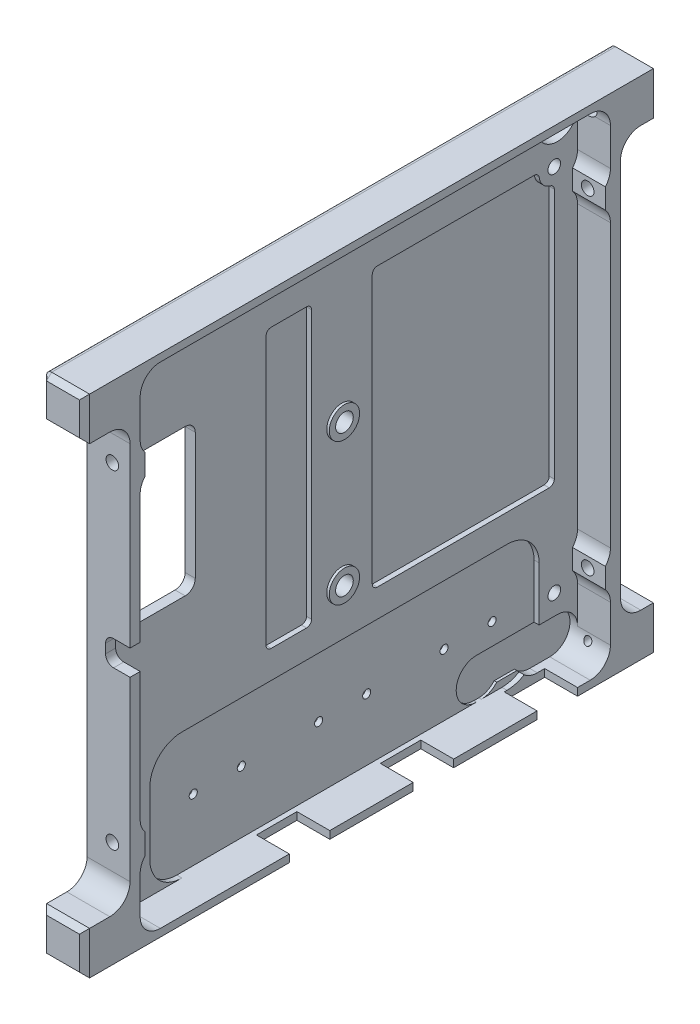
SolidWorks part; units mm, degrees
material "6061-T6 (SS)"
ref_plane "Front" through (0, 0, 0) normal (0, 0, 1) x (1, 0, 0)
ref_plane "Top" through (0, 0, 0) normal (0, 1, 0) x (1, 0, 0)
ref_plane "Right" through (0, 0, 0) normal (1, 0, 0) x (0, 0, -1)
sketch "Sketch1" plane through (0, 0, 0) normal (1, 0, 0) x (0, 0, -1)
  line L1 (0, 0) -> (-113.5, 0)
  line L2 (0, 0) -> (0, 100)
  line L3 (0, 100) -> (-113.5, 100)
  line L4 (-113.5, 0) -> (-113.5, 100)
  line L5 (-113.5, 91.5) -> (-104.5, 91.5)
  line L6 (-113.5, 91.5) -> (-113.5, 8.5)
  line L7 (-113.5, 8.5) -> (-104.5, 8.5)
  line L8 (-104.5, 91.5) -> (-104.5, 8.5)
  line L9 (0, 91.5) -> (-7.5, 91.5)
  line L10 (0, 91.5) -> (0, 8.5)
  line L11 (0, 8.5) -> (-7.5, 8.5)
  line L12 (-7.5, 91.5) -> (-7.5, 8.5)
  line L13 (-96.5, 91.5) -> (-15.5, 91.5)
  line L14 (-96.5, 91.5) -> (-96.5, 8.5)
  line L15 (-96.5, 8.5) -> (-15.5, 8.5)
  line L16 (-15.5, 91.5) -> (-15.5, 8.5)
  dimension "D1" = 113.5
  dimension "D2" = 100
  dimension "D3" = 8.5
  dimension "D4" = 8.5
  dimension "D5" = 8
  dimension "D6" = 8
  dimension "D7" = 9
  dimension "D8" = 7.5
extrude "Body" add sketch "Sketch1" along normal blind 8.5 contours L12 L9 L2 L3 L4 L5 L8 L7 L1 L11 L13 L16 L15 L14
fillet "RailFillet" radius 1 2 edges at (0, 0, 56.75) (0, 100, 56.75)
chamfer "FootChamfer" distance 1 angle 45 20 edges at (4.75, 0, 0) (8.5, 4.25, 0) (4.25, 8.5, 0) (0, 4.75, 0) (4.25, 91.5, 0) (8.5, 95.75, 0) (4.75, 100, 0) (0, 95.25, 0) (4.75, 100, 113.5) (8.5, 95.75, 113.5) (4.25, 91.5, 113.5) (0, 95.25, 113.5) (4.25, 8.5, 113.5) (8.5, 4.25, 113.5) (4.75, 0, 113.5) (0, 4.75, 113.5) (0.2929, 0.2929, 0) (0.2929, 99.7071, 0) (0.2929, 99.7071, 113.5) (0.2929, 0.2929, 113.5)
sketch "Sketch5" plane through (8.5, 0, 0) normal (1, 0, 0) x (0, 0, -1)
  line L1 (-96.5, 91.5) -> (-15.5, 91.5)
  line L2 (-96.5, 91.5) -> (-96.5, 8.5)
  line L3 (-96.5, 8.5) -> (-15.5, 8.5)
  line L4 (-15.5, 91.5) -> (-15.5, 8.5)
extrude "Boss-Extrude3" add sketch "Sketch5" against normal up to surface (8.5 mm away) up to face at (0, 50, 56.5)
sketch "Sketch6" plane through (8.5, 0, 0) normal (1, 0, 0) x (0, 0, -1)
  line L0 (-1, 100) -> (-112.5, 100) construction
  line L1 (-102.5, 98.5) -> (-9.5, 98.5)
  line L2 (-102.5, 98.5) -> (-102.5, 1.5)
  line L3 (-102.5, 1.5) -> (-9.5, 1.5)
  line L4 (-9.5, 98.5) -> (-9.5, 1.5)
  line L5 (-1, 0) -> (-112.5, 0) construction
  line L7 (-7.5, 91.5) -> (-7.5, 8.5) construction
  line L10 (-104.5, 91.5) -> (-104.5, 8.5) construction
  dimension "D1" = 1.5
  dimension "D2" = 1.5
  dimension "D3" = 2
  dimension "D4" = 2
extrude "Cut-Extrude3" cut sketch "Sketch6" against normal offset from surface (6.5 mm away) 2 up to face at (0, 50, 56.5)
sketch "Sketch4" plane through (8.5, 0, 0) normal (1, 0, 0) x (0, 0, -1)
  line L1 (-92.5, 90) -> (-19.5, 90)
  line L2 (-92.5, 90) -> (-92.5, 10)
  line L3 (-92.5, 10) -> (-19.5, 10)
  line L4 (-19.5, 90) -> (-19.5, 10)
  line L6 (-7.5, 91.5) -> (-7.5, 8.5) construction
  line L8 (-1, 100) -> (-112.5, 100) construction
  line L9 (-1, 0) -> (-112.5, 0) construction
  line L10 (-104.5, 91.5) -> (-104.5, 8.5) construction
  dimension "D1" = 12
  dimension "D2" = 10
  dimension "D3" = 10
  dimension "D4" = 12
ref_plane "Plane1" through (0, 50, 0) normal (0, 1, 0) x (1, 0, 0)
ref_plane "Plane2" through (0, 0, 56) normal (0, 0, -1) x (-1, 0, 0)
sketch "Sketch21" plane through (0, 0, 0) normal (1, 0, 0) x (0, 0, -1)
  line L0 (-98.1, 86.5) -> (-98.1, 13.5) construction
  line L1 (-98.1, 13.5) -> (-14.1, 13.5) construction
  line L2 (-14.1, 13.5) -> (-14.1, 86.5) construction
  line L3 (-14.1, 86.5) -> (-98.1, 86.5) construction
  line L4 (-14.1, 50) -> (-7.5, 50) construction
  line L6 (-7.5, 91.5) -> (-7.5, 8.5) construction
  line L7 (0, 99) -> (0, 92.5) construction
  line L8 (-14.1, 50) -> (-98.1, 50) construction
  line L9 (-56.1, 50) -> (-56.1, 36) construction
  line L10 (-7.5, 50) -> (-7.5, 0) construction
  line L11 (-112.5, 0) -> (-1, 0) construction
  line L12 (-1, 100) -> (-112.5, 100) construction
  line L13 (-7.5, 100) -> (-7.5, 50) construction
  line L16 (-56.1, 64) -> (-56.1, 50) construction
  point P3 (-14.1, 13.5)
  point P5 (-98.1, 86.5)
  point P7 (-98.1, 13.5)
  point P11 (-56.1, 36)
  point P25 (-14.1, 86.5)
  point P26 (-56.1, 64)
  dimension "D3" = 28
  dimension "D1" = 73
  dimension "D2" = 84
  dimension "D4" = 14.1
sketch "Sketch29" plane through (0, 0, 0) normal (0, 0, -1) x (-1, 0, 0)
  line L0 (-1, 92.5) -> (-7.5, 99)
  line L1 (-7.5, 99) -> (-1, 99)
  line L2 (-1, 99) -> (-4.25, 95.75)
hole_wizard "#8-36 Tapped Hole1" positions "Sketch30" profile "Sketch31" tap size "#8-36" standard "ANSI Inch"
sketch "Sketch30" plane through (0, 0, 0) normal (0, 0, -1) x (-1, 0, 0)
  point P0 (-4.25, 95.75)
sketch "Sketch31" plane through (4.25, 95.75, 0) normal (1, 0, 0) x (0, 1, 0)
  line L0 (0, 0) -> (0, 14.5878)
  line L1 (0, 14.5878) -> (1.7272, 13.55)
  line L2 (1.7272, 13.55) -> (1.7272, 0)
  line L5 (1.7272, 0) -> (0, 0)
  line L10 (0, 14.5878) -> (-1.7272, 13.55) construction
  line L11 (0, -6.35) -> (0, 107.95) construction
  dimension "Tap Drill Dia." = 3.4544
  dimension "Tap Drill Depth" = 13.55
  dimension "Drill Angle" = 118
cosmetic thread "Hole Thread1" parameters "D1"=10.5229, "D2"=4.1656
sketch "Sketch32" plane through (0, 0, 0) normal (0, 0, -1) x (-1, 0, 0)
  line L1 (-4.25, 1) -> (-4.25, 4.25) construction
  line L2 (-7.5, 1) -> (-1, 1) construction
  line L3 (-4.25, 4.25) -> (-7.5, 4.25) construction
  line L4 (-7.5, 7.5) -> (-7.5, 1) construction
  point P1 (-4.25, 4.25)
hole_wizard "#8-36 Tapped Hole2" [suppressed] positions "Sketch33" profile "Sketch34" tap size "#8-36" standard "ANSI Inch"
sketch "Sketch33" plane through (0, 0, 0) normal (0, 0, -1) x (-1, 0, 0)
  point P0 (-4.25, 4.25)
sketch "Sketch34" plane through (4.25, 4.25, 0) normal (1, 0, 0) x (0, 1, 0)
  line L0 (0, 0) -> (0, 11.4878)
  line L1 (0, 11.4878) -> (1.7272, 10.45)
  line L2 (1.7272, 10.45) -> (1.7272, 0)
  line L5 (1.7272, 0) -> (0, 0)
  line L10 (0, 11.4878) -> (-1.7272, 10.45) construction
  line L11 (0, -6.35) -> (0, 107.95) construction
  dimension "Tap Drill Dia." = 3.4544
  dimension "Tap Drill Depth" = 10.45
  dimension "Drill Angle" = 118
cosmetic thread "Hole Thread2" [suppressed] parameters "D1"=8.33, "D2"=4.1656
sketch "Sketch44" [suppressed] plane through (2.5, 0, 0) normal (1, 0, 0) x (0, 0, -1)
  point P0 (-17.45, 3.7)
  point P2 (-17.45, 7.7)
sketch "Sketch57" plane through (2, 0, 0) normal (1, 0, 0) x (0, 0, -1)
  line L0 (-9.5, 1.5) -> (-9.5, 98.5) construction
  line L1 (-9.5, 84.5) -> (-10.5, 84.5)
  line L2 (-9.5, 84.5) -> (-9.5, 80.5)
  line L3 (-9.5, 80.5) -> (-10.5, 80.5)
  line L4 (-10.5, 84.5) -> (-10.5, 80.5)
  line L5 (-102.5, 1.5) -> (-102.5, 98.5) construction
  line L6 (-9.5, 19.5) -> (-10.5, 19.5)
  line L7 (-9.5, 19.5) -> (-9.5, 15.5)
  line L8 (-9.5, 15.5) -> (-10.5, 15.5)
  line L9 (-10.5, 19.5) -> (-10.5, 15.5)
  line L10 (-10.5, 19.5) -> (-101.5, 19.5)
  line L11 (-10.5, 19.5) -> (-10.5, 15.5)
  line L12 (-10.5, 15.5) -> (-101.5, 15.5)
  line L13 (-101.5, 19.5) -> (-101.5, 15.5)
  line L14 (-10.5, 84.5) -> (-101.5, 84.5)
  line L15 (-10.5, 84.5) -> (-10.5, 80.5)
  line L16 (-10.5, 80.5) -> (-101.5, 80.5)
  line L17 (-101.5, 84.5) -> (-101.5, 80.5)
  line L18 (-101.5, 84.5) -> (-102.5, 84.5)
  line L19 (-101.5, 84.5) -> (-101.5, 80.5)
  line L20 (-101.5, 80.5) -> (-102.5, 80.5)
  line L21 (-102.5, 84.5) -> (-102.5, 80.5)
  line L22 (-9.5, 50) -> (-102.5, 50) construction
  line L23 (-101.5, 19.5) -> (-102.5, 19.5)
  line L24 (-101.5, 19.5) -> (-101.5, 15.5)
  line L25 (-101.5, 15.5) -> (-102.5, 15.5)
  line L26 (-102.5, 19.5) -> (-102.5, 15.5)
  line L28 (-102.5, 82.5) -> (-102.5, 50) construction
  line L29 (-102.5, 50) -> (-102.5, 17.5) construction
  line L31 (-9.5, 98.5) -> (-9.5, 1.5) construction
  dimension "D1" = 4
  dimension "D2" = 4
  dimension "D3" = 1
  dimension "D4" = 32.5
  dimension "D5" = 32.5
extrude "Boss-Extrude24" add sketch "Sketch57" along normal up to surface (6.5 mm away) contours L18 L21 L20 L17 | L23 L26 L25 L13 | L6 L9 L8 L7 | L1 L4 L3 L2 up to face at (8.5, 50, 56)
fillet "Fillet5" radius 4 8 edges at (5.25, 84.5, 102.5) (5.25, 19.5, 102.5) (5.25, 80.5, 102.5) (5.25, 15.5, 102.5) (5.25, 19.5, 9.5) (5.25, 15.5, 9.5) (5.25, 80.5, 9.5) (5.25, 84.5, 9.5)
sketch "Sketch59" plane through (0, 0, 7.5) normal (0, 0, -1) x (-1, 0, 0)
  line L0 (-5, 91.5) -> (-5, 82.5) construction
  line L2 (-5, 82.5) -> (-5, 17.5) construction
  line L3 (-5, 17.5) -> (-5, 8.5) construction
  line L5 (0, 91.5) -> (0, 8.5) construction
  line L6 (-8.5, 91.5) -> (0, 91.5) construction
  line L7 (-8.5, 8.5) -> (0, 8.5) construction
  dimension "D1" = 65
  dimension "D2" = 5
hole_wizard "M3x0.5 Tapped Hole1" positions "Sketch60" profile "Sketch61" tap size "M3x0.5" standard "ANSI Metric" end condition through all
sketch "Sketch60" plane through (0, 0, 7.5) normal (0, 0, -1) x (-1, 0, 0)
  point P0 (-5, 82.5)
  point P3 (-5, 17.5)
sketch "Sketch61" plane through (5, 82.5, 7.5) normal (1, 0, 0) x (0, 1, 0)
  line L0 (0, 0) -> (0, 106)
  line L1 (0, 106) -> (1.25, 106)
  line L2 (1.25, 106) -> (1.25, 0)
  line L5 (1.25, 0) -> (0, 0)
  line L11 (0, -6.35) -> (0, 107.95) construction
  dimension "Thru Tap Drill Dia." = 2.5
  dimension "Thru Tap Drill Depth" = 106
cosmetic thread "Hole Thread5" parameters "D2"=3
cosmetic thread "Hole Thread6" parameters "D2"=3
sketch "Sketch62" [suppressed] plane through (1, 0, 0) normal (1, 0, 0) x (0, 0, -1)
  line L1 (-11.25, 13.5) -> (-11.25, 1.5)
  line L2 (-11.5, 1.5) -> (-100, 1.5) construction
  line L3 (-11.25, 1.5) -> (-15.75, 1.5)
  line L4 (-15.75, 1.5) -> (-15.75, 10.1459)
  circle A0 centre (-14.75, 86.5) radius 3.5
  circle A1 centre (-14.75, 13.5) radius 3.5
  circle A2 centre (-97.75, 13.5) radius 3.5
  circle A3 centre (-97.75, 86.5) radius 3.5
  circle A4 centre (-97.75, 86.5) radius 1.25 construction
  circle A5 centre (-97.75, 13.5) radius 1.25 construction
  circle A6 centre (-14.75, 13.5) radius 1.25 construction
  circle A7 centre (-14.75, 86.5) radius 1.25 construction
  circle A8 centre (-97.75, 86.5) radius 1.25
  circle A9 centre (-97.75, 13.5) radius 1.25
  circle A10 centre (-14.75, 13.5) radius 1.25
  circle A11 centre (-14.75, 86.5) radius 1.25
  dimension "D1" = 7
  dimension "D2" = 4.5
fillet "Fillet7" radius 4 4 edges at (5.25, 98.5, 102.5) (5.25, 1.5, 102.5) (5.25, 1.5, 9.5) (5.25, 98.5, 9.5)
hole_wizard "M3x0.5 Tapped Hole2" positions "Sketch67" profile "Sketch68" tap size "M3x0.5" standard "ANSI Metric"
sketch "Sketch67" plane through (0, 0, 0) normal (-1, 0, 0) x (0, 0, 1)
  point P0 (14.1, 13.5)
  point P3 (14.1, 86.5)
  point P12 (98.1, 86.5)
  point P15 (98.1, 13.5)
sketch "Sketch68" plane through (0, 13.5, 14.1) normal (0, 1, 0) x (0, 0, 1)
  line L0 (0, 0) -> (0, 8.2511)
  line L1 (0, 8.2511) -> (1.25, 7.5)
  line L2 (1.25, 7.5) -> (1.25, 0)
  line L5 (1.25, 0) -> (0, 0)
  line L10 (0, 8.2511) -> (-1.25, 7.5) construction
  line L11 (0, -6.35) -> (0, 107.95) construction
  dimension "Tap Drill Dia." = 2.5
  dimension "Tap Drill Depth" = 7.5
  dimension "Drill Angle" = 118
cosmetic thread "Hole Thread17" parameters "D1"=2.5, "D2"=3
cosmetic thread "Hole Thread18" parameters "D1"=2.5, "D2"=3
cosmetic thread "Hole Thread21" parameters "D1"=2.5, "D2"=3
cosmetic thread "Hole Thread22" parameters "D1"=2.5, "D2"=3
fillet "Fillet8" radius 4 4 edges at (4.25, 8.5, 104.5) (4.25, 91.5, 104.5) (4.25, 8.5, 7.5) (4.25, 91.5, 7.5)
sketch "Sketch70" plane through (2, 0, 0) normal (1, 0, 0) x (0, 0, -1)
  line L0 (-13.5, 1.5) -> (-98.5, 1.5) construction
  line L2 (-13.5, 9.5) -> (-28.5, 9.5)
  line L4 (-13.5, 5.5) -> (-28.5, 5.5) construction
  line L5 (-28.5, 1.5) -> (-13.5, 1.5)
  circle A0 centre (-13.5, 94.5) radius 4
  arc A1 (-9.5, 94.5) -> (-13.5, 98.5) centre (-13.5, 94.5) ccw construction
  circle A2 centre (-13.5, 5.5) radius 4
  circle A3 centre (-28.5, 5.5) radius 4
  dimension "D1" = 15
extrude "Cut-Extrude14" cut sketch "Sketch70" against normal blind 1.5
sketch "Sketch75" plane through (0, 1.5, 0) normal (0, 1, 0) x (1, 0, 0)
  line L0 (0.5, -28.5) -> (0.5, -13.5) construction
  line L1 (0.5, -20.5) -> (8.5, -20.5)
  line L2 (0.5, -20.5) -> (0.5, -24.5)
  line L3 (0.5, -24.5) -> (8.5, -24.5)
  line L4 (8.5, -20.5) -> (8.5, -24.5)
  line L5 (8.5, -98.5) -> (8.5, -13.5) construction
  line L6 (8.5, -13.5) -> (0.5, -13.5) construction
  dimension "D1" = 7
  dimension "D2" = 4
extrude "Boss-Extrude25" add sketch "Sketch75" along normal blind 1.4
sketch "Sketch71" plane through (0, 2.9, 0) normal (0, 1, 0) x (1, 0, 0)
  line L0 (2.8, -22.5) -> (6.8, -22.5) construction
  line L1 (0.5, -28.5) -> (0.5, -24.5) construction
  dimension "D1" = 4
  dimension "D2" = 2.3
  dimension "D3" = 9
hole_wizard "M1.6x0.35 Tapped Hole1" positions "Sketch72" profile "Sketch73" tap size "M1.6x0.35" standard "ANSI Metric"
sketch "Sketch72" plane through (0, 2.9, 0) normal (0, 1, 0) x (1, 0, 0)
  point P0 (2.8, -22.5)
  point P3 (6.8, -22.5)
sketch "Sketch73" plane through (2.8, 2.9, 22.5) normal (1, 0, 0) x (0, 0, 1)
  line L0 (0, 0) -> (0, 4.6255)
  line L1 (0, 4.6255) -> (0.625, 4.25)
  line L2 (0.625, 4.25) -> (0.625, 0)
  line L5 (0.625, 0) -> (0, 0)
  line L10 (0, 4.6255) -> (-0.625, 4.25) construction
  line L11 (0, -6.35) -> (0, 107.95) construction
  dimension "Tap Drill Dia." = 1.25
  dimension "Tap Drill Depth" = 4.25
  dimension "Drill Angle" = 118
cosmetic thread "Hole Thread15" parameters "D1"=1.5, "D2"=1.6
cosmetic thread "Hole Thread16" parameters "D1"=1.5, "D2"=1.6
fillet "Fillet9" radius 4 2 edges at (4.5, 1.5, 24.5) (4.5, 1.5, 20.5)
sketch "Sketch76" plane through (0, 0, 0) normal (0, 0, -1) x (-1, 0, 0)
  line L0 (-1, 7.5) -> (-7.5, 1) construction
  point P4 (-4.25, 4.25)
hole_wizard "Ø1.5mm Dowel Hole1" positions "Sketch77" profile "Sketch79" hole size "Ø1.5" standard "ANSI Metric" end condition up to next
sketch "Sketch77" plane through (0, 0, 0) normal (0, 0, -1) x (-1, 0, 0)
  point P0 (-4.25, 4.25)
sketch "Sketch79" plane through (4.25, 4.25, 0) normal (1, 0, 0) x (0, 1, 0)
  line L0 (0, 0) -> (0, 9.7003)
  line L1 (0, 9.7003) -> (0.75, 9.7003)
  line L2 (0.75, 9.7003) -> (0.75, 0)
  line L5 (0.75, 0) -> (0, 0)
  line L11 (0, -6.35) -> (0, 107.95) construction
  dimension "Thru Hole Dia." = 1.5
  dimension "Thru Hole Depth" = 9.7003
sketch "Sketch81" plane through (2, 0, 0) normal (1, 0, 0) x (0, 0, -1)
  line L0 (-87.1, 51.5) -> (-87.1, 76.5) construction
  line L1 (-89.1, 51.5) -> (-89.1, 76.5)
  line L2 (-85.1, 51.5) -> (-85.1, 76.5)
  line L3 (-100.5, 51.5) -> (-100.5, 76.5) construction
  line L4 (-102.5, 51.5) -> (-102.5, 76.5)
  line L5 (-98.5, 51.5) -> (-98.5, 76.5)
  line L6 (-87.1, 51.5) -> (-100.5, 51.5) construction
  line L7 (-87.1, 49.5) -> (-100.5, 49.5)
  line L8 (-87.1, 76.5) -> (-100.5, 76.5) construction
  line L9 (-87.1, 78.5) -> (-100.5, 78.5)
  line L10 (-102.5, 22.1458) -> (-102.5, 77.8542) construction
  arc A0 (-89.1, 51.5) -> (-85.1, 51.5) centre (-87.1, 51.5) ccw
  arc A1 (-85.1, 76.5) -> (-89.1, 76.5) centre (-87.1, 76.5) ccw
  arc A2 (-102.5, 51.5) -> (-98.5, 51.5) centre (-100.5, 51.5) ccw
  arc A3 (-98.5, 76.5) -> (-102.5, 76.5) centre (-100.5, 76.5) ccw
  circle A6 centre (-98.1, 86.5) radius 1.25 construction
  point P2 (-87.1, 64)
  point P7 (-100.5, 64)
  line M19 (-102.5, 77.8542) -> (-102.5, 22.1458)
  dimension "D2" = 2
  dimension "D3" = 2
  dimension "D5" = 10
  dimension "D1" = 11
  dimension "D4" = 25
extrude "Cut-Extrude15" cut sketch "Sketch81" against normal through all contours L5 A3 A2 M19 | L2 A1 L1 A0 | A3 L5 A2 L7 A0 L1 A1 L9
sketch "Sketch84" plane through (0, 0, 0) normal (-1, 0, 0) x (0, 0, 1)
  line L0 (112.5, 0) -> (1, 0) construction
  line L1 (7.5, 87.5) -> (7.5, 12.5) construction
  circle A0 centre (56.1, 36) radius 1.75
  circle A1 centre (56.1, 64) radius 1.75
  dimension "D1" = 3.5
  dimension "D4" = 64
  dimension "D2" = 36
  dimension "D3" = 48.6
extrude "Cut-Extrude17" cut sketch "Sketch84" against normal through all
sketch "Sketch85" plane through (0, 0, 104.5) normal (0, 0, 1) x (1, 0, 0)
  line L0 (8.5, 50) -> (-8.6319, 50) construction
  line L1 (8.5, 87.5) -> (8.5, 12.5) construction
  line L6 (5.25, 47.5) -> (8.5, 47.5)
  line L7 (8.5, 47.5) -> (8.5, 52.5)
  line L8 (8.5, 52.5) -> (5.25, 52.5)
  line L9 (3.66, 49.09) -> (3.66, 50.91)
  arc A1 (3.66, 50.91) -> (5.25, 52.5) centre (5.25, 50.91) cw
  arc A2 (3.66, 49.09) -> (5.25, 47.5) centre (5.25, 49.09) ccw
  dimension "D1" = 1.59
  dimension "D4" = 3.25
  dimension "D2" = 5
  dimension "D3" = 2.5
extrude "Cut-Extrude18" cut sketch "Sketch85" against normal up to surface (2 mm away) up to face at (5.25, 90.8229, 102.5)
sketch "Sketch86" plane through (2, 0, 0) normal (1, 0, 0) x (0, 0, -1)
  line L0 (-104.5, 87.5) -> (-104.5, 52.5) construction
  line L1 (-25.4, 13.75) -> (-84.5, 13.75) construction
  line L2 (-1, 0) -> (-112.5, 0) construction
  circle A2 centre (-50.2, 13.75) radius 0.8
  circle A3 centre (-59.7, 13.75) radius 0.8
  circle A4 centre (-75, 13.75) radius 0.8
  circle A5 centre (-84.5, 13.75) radius 0.8
  circle A6 centre (-34.9, 13.75) radius 0.8
  circle A7 centre (-25.4, 13.75) radius 0.8
  dimension "D1" = 1.6
  dimension "D2" = 20
  dimension "D3" = 13.75
  dimension "D4" = 9.5
  dimension "D6" = 15.3
  dimension "D7" = 9.5
  dimension "D10" = 15.3
  dimension "D12" = 9.5
extrude "Cut-Extrude19" cut sketch "Sketch86" against normal through all
cosmetic thread "Hole Thread23" parameters "D1"=1, "D2"=2
cosmetic thread "Hole Thread24" parameters "D1"=1, "D2"=2
cosmetic thread "Hole Thread25" parameters "D1"=1, "D2"=2
cosmetic thread "Hole Thread26" parameters "D1"=1, "D2"=2
cosmetic thread "Hole Thread27" parameters "D1"=1, "D2"=2
cosmetic thread "Hole Thread28" parameters "D1"=1, "D2"=2
sketch "Sketch90" plane through (2, 0, 0) normal (1, 0, 0) x (0, 0, -1)
  line L1 (-87.75, 1.5) -> (-23.45, 1.5)
  line L2 (-94.1, 7.85) -> (-94.1, 20.15)
  line L3 (-87.75, 26.5) -> (-23.45, 26.5)
  line L4 (-17.1, 7.85) -> (-17.1, 20.15)
  line L5 (-102.5, 47.5) -> (-102.5, 22.1458) construction
  line L6 (-98.5, 1.5) -> (-27.5397, 1.5) construction
  arc A0 (-23.45, 1.5) -> (-17.1, 7.85) centre (-23.45, 7.85) ccw
  arc A1 (-23.45, 26.5) -> (-17.1, 20.15) centre (-23.45, 20.15) cw
  arc A2 (-87.75, 1.5) -> (-94.1, 7.85) centre (-87.75, 7.85) cw
  arc A3 (-94.1, 20.15) -> (-87.75, 26.5) centre (-87.75, 20.15) cw
  dimension "D1" = 6.35
  dimension "D2" = 77
  dimension "D3" = 25
  dimension "D4" = 8.4
extrude "Cut-Extrude21" cut sketch "Sketch90" against normal blind 1 and the other way through all
sketch "Sketch91" plane through (0, 0, 0) normal (0, -1, 0) x (1, 0, 0)
  line L0 (8.5, 1) -> (8.5, 112.5) construction
  line L1 (8.5, 16) -> (2, 16)
  line L2 (8.5, 16) -> (8.5, 24)
  line L3 (8.5, 24) -> (2, 24)
  line L4 (2, 16) -> (2, 24)
  line L5 (7.5, 0) -> (1, 0) construction
  line L6 (2, 40.5) -> (2, 48.5)
  line L7 (8.5, 48.5) -> (2, 48.5)
  line L8 (8.5, 40.5) -> (8.5, 48.5)
  line L9 (8.5, 40.5) -> (2, 40.5)
  line L10 (2, 65) -> (2, 73)
  line L11 (8.5, 73) -> (2, 73)
  line L12 (8.5, 65) -> (8.5, 73)
  line L13 (8.5, 65) -> (2, 65)
  dimension "D1" = 6.5
  dimension "D2" = 8
  dimension "D3" = 16
  dimension "D5" = 16.5
  dimension "D4" = 3
extrude "Cut-Extrude22" cut sketch "Sketch91" against normal blind 10
sketch "Sketch93" plane through (2, 0, 0) normal (1, 0, 0) x (0, 0, -1)
  circle A0 centre (-56.1, 64) radius 3
  circle A1 centre (-56.1, 36) radius 3
  circle A2 centre (-56.1, 64) radius 1.75
  circle A3 centre (-56.1, 36) radius 1.75
  circle A4 centre (-56.1, 36) radius 1.75 construction
  circle A5 centre (-56.1, 64) radius 1.75 construction
  dimension "D1" = 6
  dimension "D2" = 6
extrude "Boss-Extrude26" add sketch "Sketch93" along normal blind 0.5
sketch "Sketch94" plane through (2, 0, 0) normal (1, 0, 0) x (0, 0, -1)
  line L0 (-112.5, 0) -> (-1, 0) construction
  line L1 (-18.07, 87) -> (-49.1, 87)
  line L3 (-15.1, 32) -> (-49.1, 32)
  line L4 (-50.1, 86) -> (-50.1, 33)
  line L5 (-14.1, 87) -> (-50.1, 32) construction
  line L6 (-14.3929, 32.2929) -> (-50.1, 87) construction
  line L7 (-18.07, 87) -> (-14.1, 87) construction
  line L8 (-14.1, 33) -> (-14.1, 82.63)
  line L9 (-14.1, 87) -> (-14.1, 82.63) construction
  line L10 (-7.5, 87.5) -> (-7.5, 12.5) construction
  line L12 (-70.1, 32) -> (-63.1, 32)
  line L13 (-71.1, 33) -> (-71.1, 86)
  line L14 (-70.1, 87) -> (-63.1, 87)
  line L15 (-62.1, 33) -> (-62.1, 86)
  arc A0 (-49.1, 32) -> (-50.1, 33) centre (-49.1, 33) cw
  arc A1 (-14.1, 33) -> (-15.1, 32) centre (-15.1, 33) cw
  arc A3 (-49.1, 87) -> (-50.1, 86) centre (-49.1, 86) ccw
  arc A4 (-17.078, 86.1259) -> (-14.8505, 83.5984) centre (-14.1018, 86.5035) ccw
  arc A5 (-14.1, 82.63) -> (-14.8505, 83.5984) centre (-15.1, 82.63) ccw
  arc A6 (-18.07, 87) -> (-17.078, 86.1259) centre (-18.07, 86) cw
  arc A7 (-70.1, 32) -> (-71.1, 33) centre (-70.1, 33) cw
  arc A8 (-63.1, 32) -> (-62.1, 33) centre (-63.1, 33) ccw
  arc A9 (-63.1, 87) -> (-62.1, 86) centre (-63.1, 86) cw
  arc A10 (-71.1, 86) -> (-70.1, 87) centre (-70.1, 86) cw
  point P0 (-32.1255, 59.4611)
  dimension "D5" = 1
  dimension "D3" = 1
  dimension "D6" = 3
  dimension "D10" = 1
  dimension "D12" = 1
  dimension "D1" = 32
  dimension "D2" = 55
  dimension "D4" = 36
  dimension "D7" = 31.03
  dimension "D8" = 49.63
  dimension "D9" = 6.6
  dimension "D11" = 9
  dimension "D13" = 12
extrude "Cut-Extrude23" cut sketch "Sketch94" against normal blind 1
hole_wizard "M2x0.4 Tapped Hole1" positions "3DSketch1" profile "Sketch95" tap size "M2x0.4" standard "ANSI Metric"
sketch3d "3DSketch1"
  line L0 (0, 13.75, 84.5) -> (1, 13.75, 84.5) construction
  line L1 (0, 13.75, 75) -> (1, 13.75, 75) construction
  line L2 (0, 13.75, 59.7) -> (1, 13.75, 59.7) construction
  line L3 (0, 13.75, 50.2) -> (1, 13.75, 50.2) construction
  line L4 (0, 13.75, 34.9) -> (1, 13.75, 34.9) construction
  line L5 (0, 13.75, 25.4) -> (1, 13.75, 25.4) construction
  point P0 (1, 13.75, 84.5)
  point P4 (1, 13.75, 75)
  point P8 (1, 13.75, 59.7)
  point P12 (1, 13.75, 50.2)
  point P16 (1, 13.75, 34.9)
  point P20 (1, 13.75, 25.4)
sketch "Sketch95" plane through (1, 13.75, 84.5) normal (0, 1, 0) x (0, 0, -1)
  line L0 (0, 0) -> (0, 5.6807)
  line L1 (0, 5.6807) -> (0.8, 5.2)
  line L2 (0.8, 5.2) -> (0.8, 0)
  line L5 (0.8, 0) -> (0, 0)
  line L10 (0, 5.6807) -> (-0.8, 5.2) construction
  line L11 (0, -6.35) -> (0, 107.95) construction
  dimension "Tap Drill Dia." = 1.6
  dimension "Tap Drill Depth" = 5.2
  dimension "Drill Angle" = 118
